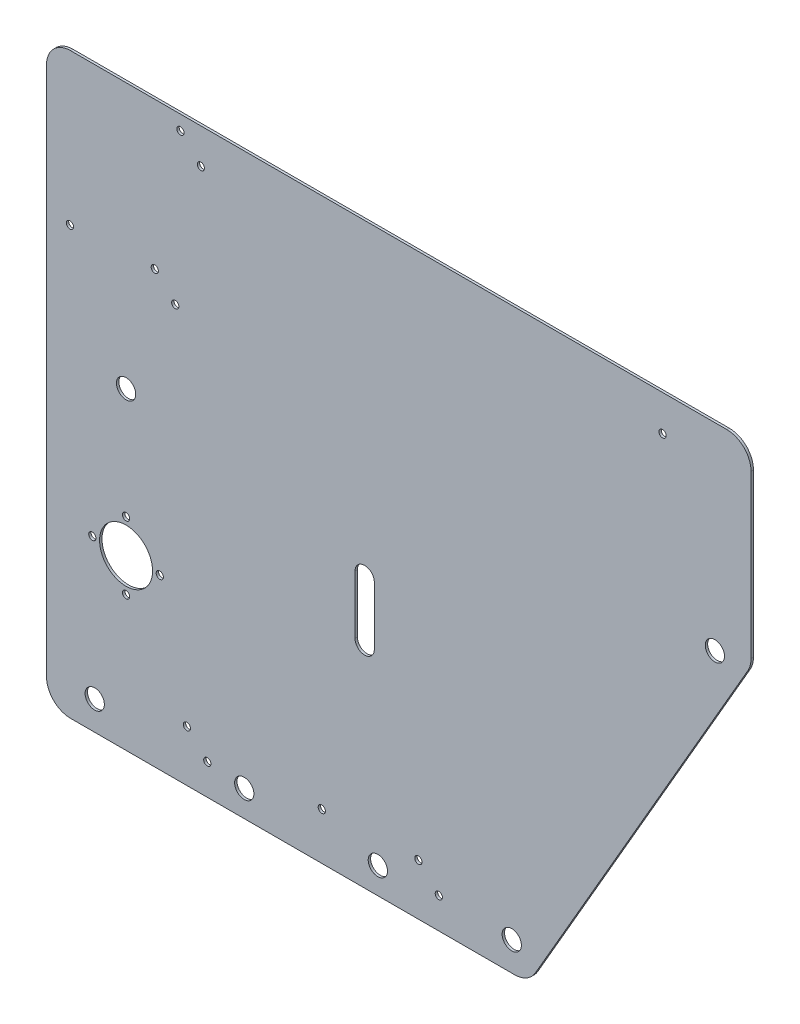
SolidWorks part; units mm, degrees
ref_plane "Front Plane" through (0, 0, 0) normal (0, 0, 1) x (1, 0, 0)
ref_plane "Top Plane" through (0, 0, 0) normal (0, 1, 0) x (1, 0, 0)
ref_plane "Right Plane" through (0, 0, 0) normal (1, 0, 0) x (0, 0, -1)
sketch "Sketch1" plane through (0, 0, 0) normal (0, 0, 1) x (1, 0, 0)
  line L0 (100, 80) -> (192.376, 80)
  line L1 (-100, -80) -> (100, -80)
  line L2 (-100, -80) -> (-100, 80)
  line L3 (-100, 80) -> (100, 80)
  line L4 (100, -80) -> (100, 80)
  line L5 (-100, -80) -> (100, 80) construction
  line L6 (-100, 80) -> (100, -80) construction
  line L7 (192.376, 80) -> (100, -80)
  line L8 (100, 80) -> (100, -80)
  line L10 (-100, 80) -> (192.376, 80)
  line L11 (-100, 80) -> (-100, 110)
  line L12 (-100, 110) -> (192.376, 110)
  line L13 (192.376, 80) -> (192.376, 110)
  point P0 (0, 0)
  dimension "D1" = 160
  dimension "D2" = 200
  dimension "D3" = 30
  dimension "D4" = 30
extrude "Boss-Extrude1" add sketch "Sketch1" along normal blind 1 contours L1 L4 L3 L2 | L7 L0 L4 | L11 L10 L13 L12 region at (0, 0, 0) region at (130.792, 26.6667, 0)
sketch "Sketch2" plane through (0, 0, 1) normal (0, 0, 1) x (1, 0, 0)
  line L0 (-100, -80) -> (100, -80) construction
  line L1 (192.376, 80) -> (100, -80) construction
  line L2 (-100, -80) -> (-100, 110) construction
  line L3 (-100, 110) -> (192.376, 110) construction
  line L4 (-67, -10) -> (-67, 70) construction
  line L7 (-100, -80) -> (-100, 110) construction
  line L15 (-100, -80) -> (-100, 110) construction
  line L18 (32.0262, 32) -> (32.0262, 7.7776) construction
  line L19 (36.0262, 32) -> (36.0262, 7.7776)
  line L20 (28.0262, 32) -> (28.0262, 7.7776)
  circle A0 centre (93.0718, -68) radius 4
  circle A1 centre (177.3649, 78) radius 4
  circle A2 centre (-67, -10) radius 11
  circle A3 centre (-80, -68) radius 4
  circle A4 centre (-53, -10) radius 1.5
  circle A5 centre (-67, 4) radius 1.5
  circle A6 centre (-81, -10) radius 1.5
  circle A7 centre (-67, -24) radius 1.5
  circle A10 centre (32.0262, 20) radius 4 construction
  circle A32 centre (62.7961, -67.2426) radius 1.5
  circle A33 centre (54.3108, -58.7574) radius 1.5
  circle A34 centre (-33.2742, -67.2426) radius 1.5
  circle A35 centre (-41.7595, -58.7574) radius 1.5
  circle A36 centre (14.2259, -60.5) radius 1.5
  circle A37 centre (-46.589, 90.4743) radius 1.5
  circle A38 centre (-55.0743, 98.9596) radius 1.5
  circle A39 centre (-90.2956, 97.2169) radius 1.5
  circle A40 centre (155.6518, 145.1456) radius 1.5
  arc A41 (36.0262, 32) -> (28.0262, 32) centre (32.0262, 32) ccw
  arc A42 (28.0262, 7.7776) -> (36.0262, 7.7776) centre (32.0262, 7.7776) ccw
  circle A43 centre (-17.9479, -69.1174) radius 4
  circle A44 centre (37.4944, -69.1174) radius 4
  circle A45 centre (-67, -10) radius 40 construction
  circle A46 centre (-67, 50) radius 20 construction
  circle A47 centre (-67, 50) radius 4
  point P65 (32.0262, 19.8888)
  dimension "D3" = 8
  dimension "D4" = 8
  dimension "D9" = 22
  dimension "D10" = 8
  dimension "D12" = 3
  dimension "D13" = 3
  dimension "D14" = 3
  dimension "D15" = 3
  dimension "D16" = 14
  dimension "D20" = 60
  dimension "D22" = 8
  dimension "D23" = 3
  dimension "D24" = 20
  dimension "D25" = 3
  dimension "D26" = 40
  dimension "D27" = 8
  dimension "D1" = 12
  dimension "D2" = 12
  dimension "D5" = 32
  dimension "D6" = 12
  dimension "D7" = 33
  dimension "D8" = 70
  dimension "D11" = 12
  dimension "D17" = 14
  dimension "D18" = 14
  dimension "D19" = 14
  dimension "D21" = 90
  dimension "D28" = 4
  dimension "D29" = 24.2224
  dimension "D30" = 12
  dimension "D31" = 132.0262
extrude "Cut-Extrude1" cut sketch "Sketch2" against normal blind 3
sketch "Sketch3" plane through (0, 0, 1) normal (0, 0, 1) x (1, 0, 0)
  line L0 (192.376, 80) -> (192.376, 110) construction
  line L1 (-100, 110) -> (192.376, 110)
  line L2 (-100, 110) -> (-100, 160)
  line L3 (-100, 160) -> (192.376, 160)
  line L4 (192.376, 110) -> (192.376, 160)
  dimension "D1" = 50
extrude "Boss-Extrude2" add sketch "Sketch3" against normal blind 1
fillet "Fillet1" radius 10 5 edges at (100, -80, 0.5) (-100, -80, 0.5) (-100, 160, 0.5) (192.376, 160, 0.5) (192.376, 80, 0.5)
sketch "Sketch4" plane through (0, 0, 1) normal (0, 0, 1) x (1, 0, 0)
  circle A2 centre (-44.4423, 153.9596) radius 1.5
  circle A3 centre (-35.957, 145.4743) radius 1.5
  circle A4 centre (155.6518, 145.1456) radius 1.5
  dimension "D1" = 3
extrude "Cut-Extrude2" cut sketch "Sketch4" against normal blind 11
